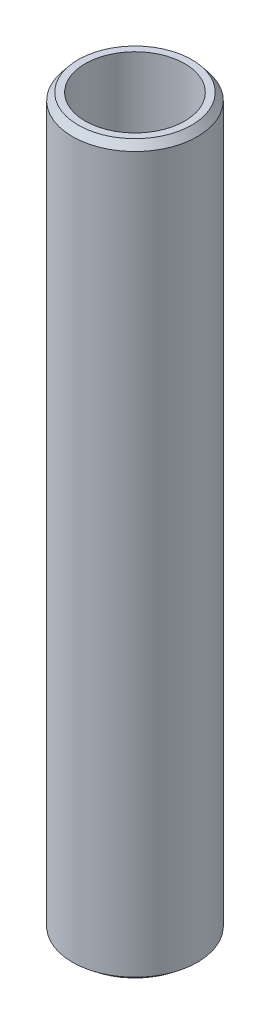
SolidWorks part; units mm, degrees
ref_plane "Front Plane" through (0, 0, 0) normal (0, 0, 1) x (1, 0, 0)
ref_plane "Top Plane" through (0, 0, 0) normal (0, 1, 0) x (1, 0, 0)
ref_plane "Right Plane" through (0, 0, 0) normal (1, 0, 0) x (0, 0, -1)
sketch "Sketch1" plane through (0, 0, 0) normal (0, 1, 0) x (1, 0, 0)
  circle A0 centre (0, 0) radius 22.5
  dimension "SHAFT_OD" = 45
extrude "Boss-Extrude1" add sketch "Sketch1" along normal blind 262.1455
sketch "Sketch2" plane through (0, 0, 0) normal (0, 1, 0) x (1, 0, 0)
  circle A0 centre (0, 0) radius 17.9255
  dimension "BORE_D" = 35.8511
extrude "Cut-Extrude1" cut sketch "Sketch2" along normal through all
chamfer "Chamfer1" distance 2.5659 angle 38.681 2 edges at (0, 262.1455, 22.5) (0, 0, 22.5) first distance on face at (0, 262.1455, 22.5) first distance on face at (0, 0, 17.9255)
